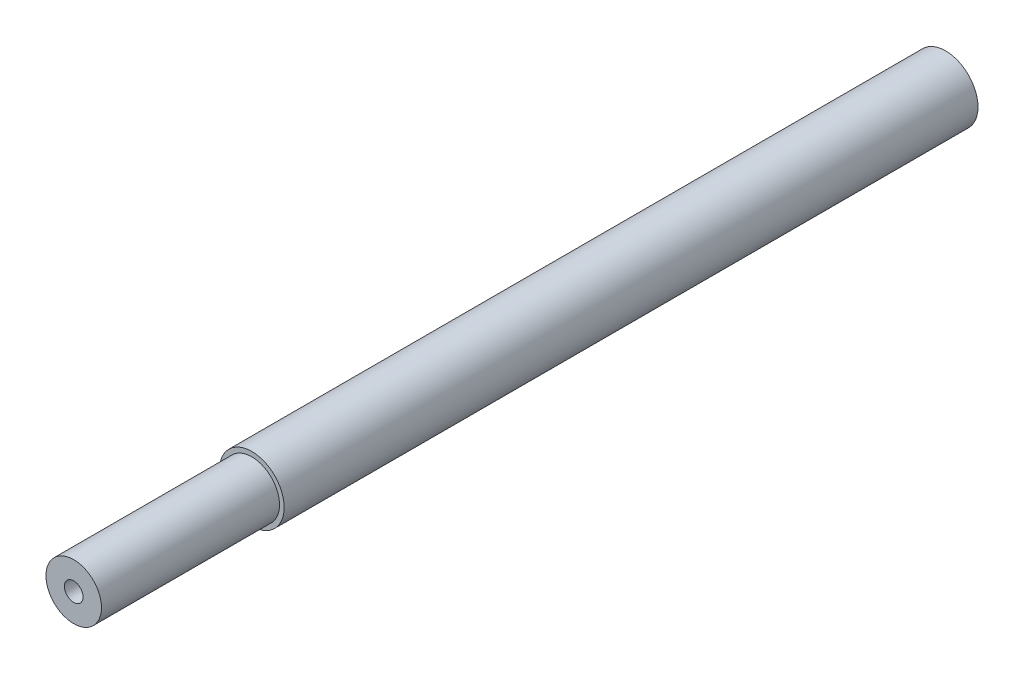
SolidWorks part; units mm, degrees
ref_plane "Front Plane" through (0, 0, 0) normal (0, 0, 1) x (1, 0, 0)
ref_plane "Top Plane" through (0, 0, 0) normal (0, 1, 0) x (1, 0, 0)
ref_plane "Right Plane" through (0, 0, 0) normal (1, 0, 0) x (0, 0, -1)
sketch "Sketch1" plane through (0, 0, 0) normal (1, 0, 0) x (0, 0, -1)
  line L0 (0, 0) -> (146.042, 0) construction
  line L1 (183, 0) -> (183, 7)
  line L3 (-5.5, 6) -> (-5.5, 0)
  line L4 (-5.5, 0) -> (183, 0)
  line L5 (-5.5, 6) -> (33, 6)
  line L6 (33, 6) -> (33, 7)
  line L7 (33, 7) -> (183, 7)
  line L8 (-6, 6) -> (-6, -6) construction
  line L9 (33, -12) -> (33, 12) construction
  line L10 (33, -32.7722) -> (33, 45) construction
  point P9 (88.124, 11.1634)
  point P14 (33, 7.0191)
  dimension "D1" = 12
  dimension "D2" = 0.5
  dimension "D3" = 14
  dimension "D4" = 150
revolve "Revolve1" add sketch "Sketch1" angle 360 about L0
sketch "Sketch2" plane through (0, 0, 5.5) normal (0, 0, 1) x (1, 0, 0)
  circle A0 centre (0, 0) radius 2.0193
  dimension "D1" = 4.0386
extrude "Cut-Extrude1" cut sketch "Sketch2" against normal blind 25
